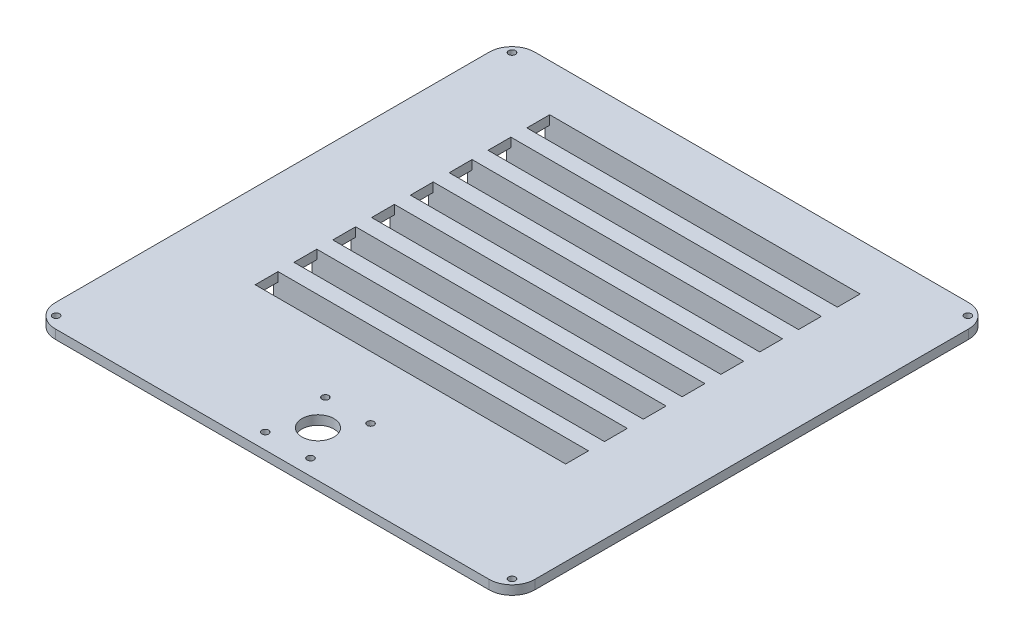
SolidWorks part; units mm, degrees
ref_plane "Front Plane" through (0, 0, 0) normal (0, 0, 1) x (1, 0, 0)
ref_plane "Top Plane" through (0, 0, 0) normal (0, 1, 0) x (1, 0, 0)
ref_plane "Right Plane" through (0, 0, 0) normal (1, 0, 0) x (0, 0, -1)
sketch "Sketch1" plane through (0, 0, 0) normal (0, 1, 0) x (1, 0, 0)
  line L0 (-101, -101) -> (-101, 101)
  line L5 (-105, -105) -> (105, -105)
  line L6 (-105, -105) -> (-105, 105)
  line L7 (-105, 105) -> (105, 105)
  line L8 (105, -105) -> (105, 105)
  line L9 (-101, 101) -> (101, 101)
  line L10 (101, -101) -> (101, 101)
  line L11 (-101, -101) -> (101, -101)
  line L12 (-101, 101) -> (-99.8333, 99.8333) construction
  line L13 (-55, 0) -> (55, 0) construction
  line L14 (-101, -101) -> (-99.8333, -99.8333) construction
  line L15 (0, -55) -> (0, 55) construction
  line L16 (101, -101) -> (99.8333, -99.8333) construction
  line L17 (101, 101) -> (99.8333, 99.8333) construction
  circle A1 centre (-99.8333, 99.8333) radius 1.5
  circle A2 centre (-99.8333, -99.8333) radius 1.5
  circle A3 centre (99.8333, -99.8333) radius 1.5
  circle A4 centre (99.8333, 99.8333) radius 1.5
  point P0 (0, 0)
  point P6 (-105, 0)
  point P7 (0, 105)
  dimension "D3" = 4
  dimension "D4" = 3
  dimension "D1" = 210
  dimension "D2" = 210
  dimension "D5" = 1.65
  dimension "D6" = 45
extrude "MainExtrude" add sketch "Sketch1" along normal blind 4 contours L6 L5 L8 L7
extrude "ScrewHoles" cut sketch "Sketch1<6>" along normal up to surface (4 mm away) contours A1 | A2 | A3 | A4 up to face at (0, 4, 0)
sketch "Sketch1<6>" plane through (0, 0, 0) normal (0, 1, 0) x (1, 0, 0) same geometry as "Sketch1"
fillet "RoundedCorners" radius 10 4 edges at (-105, 2, -105) (-105, 2, 105) (105, 2, -105) (105, 2, 105)
sketch "Sketch3" plane through (0, 0, 0) normal (0, 1, 0) x (1, 0, 0)
  line L145 (-68, 96.5) -> (68, 96.5) construction
  line L146 (-68, 96.5) -> (-68, -56.5) construction
  line L147 (-68, -56.5) -> (68, -56.5) construction
  line L148 (68, 96.5) -> (68, -56.5) construction
  line L149 (-68, 96.5) -> (68, -56.5) construction
  line L151 (68, 96.5) -> (-68, -56.5) construction
  line L152 (-68, 79.5) -> (68, 79.5) construction
  line L154 (-68, 62.5) -> (68, 62.5) construction
  line L155 (-68, 45.5) -> (68, 45.5) construction
  line L157 (-68, 28.5) -> (68, 28.5) construction
  line L158 (-68, 11.5) -> (68, 11.5) construction
  line L159 (-68, -5.5) -> (68, -5.5) construction
  line L160 (-68, -22.5) -> (68, -22.5) construction
  line L161 (-68, -39.5) -> (68, -39.5) construction
  line L162 (-68, 74.5) -> (68, 74.5)
  line L163 (-68, 57.5) -> (68, 57.5)
  line L164 (-68, 40.5) -> (68, 40.5)
  line L165 (-68, 23.5) -> (68, 23.5)
  line L166 (-68, 6.5) -> (68, 6.5)
  line L167 (-68, -10.5) -> (68, -10.5)
  line L168 (-68, -27.5) -> (68, -27.5)
  line L169 (-68, -44.5) -> (68, -44.5)
  line L170 (-68, 84.5) -> (68, 84.5)
  line L171 (-68, 67.5) -> (68, 67.5)
  line L172 (-68, 50.5) -> (68, 50.5)
  line L173 (-68, 33.5) -> (68, 33.5)
  line L174 (-68, 16.5) -> (68, 16.5)
  line L175 (-68, -0.5) -> (68, -0.5)
  line L176 (-68, -17.5) -> (68, -17.5)
  line L177 (-68, -34.5) -> (68, -34.5)
  line L178 (-68, 74.5) -> (-68, 84.5)
  line L179 (68, 74.5) -> (68, 84.5)
  line L180 (-68, 57.5) -> (-68, 67.5)
  line L181 (68, 57.5) -> (68, 67.5)
  line L182 (-68, 40.5) -> (-68, 50.5)
  line L183 (68, 40.5) -> (68, 50.5)
  line L184 (-68, 23.5) -> (-68, 33.5)
  line L185 (68, 23.5) -> (68, 33.5)
  line L186 (-68, 6.5) -> (-68, 16.5)
  line L187 (68, 6.5) -> (68, 16.5)
  line L188 (-68, -10.5) -> (-68, -0.5)
  line L189 (68, -10.5) -> (68, -0.5)
  line L190 (-68, -27.5) -> (-68, -17.5)
  line L191 (68, -27.5) -> (68, -17.5)
  line L192 (-68, -44.5) -> (-68, -34.5)
  line L193 (68, -44.5) -> (68, -34.5)
  line L194 (-99, -51) -> (-18, -51) construction
  line L195 (-99, -51) -> (-99, -94) construction
  line L196 (-99, -94) -> (-18, -94) construction
  line L197 (-18, -51) -> (-18, -94) construction
  line L198 (-99, -51) -> (-18, -94) construction
  line L199 (-99, -94) -> (-18, -51) construction
  line L200 (-9.9, -71.85) -> (-9.9, -98.15) construction
  line L201 (-95, -105) -> (95, -105) construction
  line L202 (-105, -95) -> (-105, 95) construction
  line L207 (-97.2358, 20) -> (95.5763, 20) construction
  line L208 (-9.9, -71.85) -> (9.9, -71.85) construction
  circle A0 centre (0, -85) radius 7
  circle A1 centre (-9.9, -71.85) radius 1.5
  circle A2 centre (-9.9, -98.15) radius 1.5
  circle A3 centre (9.9, -98.15) radius 1.5
  circle A4 centre (9.9, -71.85) radius 1.5
  circle A5 centre (-99.8333, -99.8333) radius 1.5 construction
  point P56 (-9.9, -85)
  point P69 (0, -71.85)
  point P70 (0, 20)
  point P71 (0, 0)
  dimension "D18" = 14
  dimension "D19" = 20
  dimension "D21" = 40.5
  dimension "D23" = 6
  dimension "D25" = 3
  dimension "D26" = 3
  dimension "D27" = 19.8
  dimension "D1" = 136
  dimension "D2" = 153
  dimension "D3" = 17
  dimension "D4" = 17
  dimension "D5" = 17
  dimension "D6" = 17
  dimension "D7" = 17
  dimension "D8" = 17
  dimension "D9" = 17
  dimension "D11" = 17
  dimension "D13" = 5
  dimension "D14" = 129
  dimension "D10" = 17
  dimension "D12" = 5
  dimension "D15" = 81
  dimension "D17" = 11
  dimension "D16" = 43
  dimension "D20" = 20
  dimension "D22" = 6.5
  dimension "D28" = 26.3
  dimension "D30" = 5.8333
extrude "Trench" cut sketch "Sketch3" along normal blind 10
sketch "Sketch4" plane through (0, 0, 0) normal (0, 1, 0) x (1, 0, 0)
  line L0 (68, -34.5) -> (68, -44.5) construction
  line L1 (68, -44.5) -> (-68, -44.5) construction
  line L2 (-68, -44.5) -> (-68, -34.5) construction
  line L3 (-68, -34.5) -> (68, -34.5) construction
  line L4 (68, -17.5) -> (68, -27.5) construction
  line L5 (68, -27.5) -> (-68, -27.5) construction
  line L6 (-68, -27.5) -> (-68, -17.5) construction
  line L7 (-68, -17.5) -> (68, -17.5) construction
  line L8 (68, -0.5) -> (68, -10.5) construction
  line L9 (68, -10.5) -> (-68, -10.5) construction
  line L10 (-68, -10.5) -> (-68, -0.5) construction
  line L11 (-68, -0.5) -> (68, -0.5) construction
  line L12 (68, 16.5) -> (68, 6.5) construction
  line L13 (68, 6.5) -> (-68, 6.5) construction
  line L14 (-68, 6.5) -> (-68, 16.5) construction
  line L15 (-68, 16.5) -> (68, 16.5) construction
  line L16 (68, 33.5) -> (68, 23.5) construction
  line L17 (68, 23.5) -> (-68, 23.5) construction
  line L18 (-68, 23.5) -> (-68, 33.5) construction
  line L19 (-68, 33.5) -> (68, 33.5) construction
  line L20 (68, 50.5) -> (68, 40.5) construction
  line L21 (68, 40.5) -> (-68, 40.5) construction
  line L22 (-68, 40.5) -> (-68, 50.5) construction
  line L23 (-68, 50.5) -> (68, 50.5) construction
  line L24 (68, 67.5) -> (68, 57.5) construction
  line L25 (68, 57.5) -> (-68, 57.5) construction
  line L26 (-68, 57.5) -> (-68, 67.5) construction
  line L27 (-68, 67.5) -> (68, 67.5) construction
  line L28 (68, 84.5) -> (68, 74.5) construction
  line L29 (68, 74.5) -> (-68, 74.5) construction
  line L30 (-68, 74.5) -> (-68, 84.5) construction
  line L31 (-68, 84.5) -> (68, 84.5) construction
  line L32 (68, -34.5) -> (68, -44.5)
  line L33 (68, -44.5) -> (-68, -44.5)
  line L34 (-68, -44.5) -> (-68, -34.5)
  line L35 (-68, -34.5) -> (68, -34.5)
  line L36 (68, -17.5) -> (68, -27.5)
  line L37 (68, -27.5) -> (-68, -27.5)
  line L38 (-68, -27.5) -> (-68, -17.5)
  line L39 (-68, -17.5) -> (68, -17.5)
  line L40 (68, -0.5) -> (68, -10.5)
  line L41 (68, -10.5) -> (-68, -10.5)
  line L42 (-68, -10.5) -> (-68, -0.5)
  line L43 (-68, -0.5) -> (68, -0.5)
  line L44 (68, 16.5) -> (68, 6.5)
  line L45 (68, 6.5) -> (-68, 6.5)
  line L46 (-68, 6.5) -> (-68, 16.5)
  line L47 (-68, 16.5) -> (68, 16.5)
  line L48 (68, 33.5) -> (68, 23.5)
  line L49 (68, 23.5) -> (-68, 23.5)
  line L50 (-68, 23.5) -> (-68, 33.5)
  line L51 (-68, 33.5) -> (68, 33.5)
  line L52 (68, 50.5) -> (68, 40.5)
  line L53 (68, 40.5) -> (-68, 40.5)
  line L54 (-68, 40.5) -> (-68, 50.5)
  line L55 (-68, 50.5) -> (68, 50.5)
  line L56 (68, 67.5) -> (68, 57.5)
  line L57 (68, 57.5) -> (-68, 57.5)
  line L58 (-68, 57.5) -> (-68, 67.5)
  line L59 (-68, 67.5) -> (68, 67.5)
  line L60 (68, 84.5) -> (68, 74.5)
  line L61 (68, 74.5) -> (-68, 74.5)
  line L62 (-68, 74.5) -> (-68, 84.5)
  line L63 (-68, 84.5) -> (68, 84.5)
  line L64 (70, 86.5) -> (70, 72.5)
  line L65 (70, 72.5) -> (-70, 72.5)
  line L66 (-70, 72.5) -> (-70, 86.5)
  line L67 (-70, 86.5) -> (70, 86.5)
  line L68 (70, 69.5) -> (70, 55.5)
  line L69 (70, 55.5) -> (-70, 55.5)
  line L70 (-70, 55.5) -> (-70, 69.5)
  line L71 (-70, 69.5) -> (70, 69.5)
  line L72 (70, 52.5) -> (70, 38.5)
  line L73 (70, 38.5) -> (-70, 38.5)
  line L74 (-70, 38.5) -> (-70, 52.5)
  line L75 (-70, 52.5) -> (70, 52.5)
  line L76 (70, 35.5) -> (70, 21.5)
  line L77 (70, 21.5) -> (-70, 21.5)
  line L78 (-70, 21.5) -> (-70, 35.5)
  line L79 (-70, 35.5) -> (70, 35.5)
  line L80 (70, 18.5) -> (70, 4.5)
  line L81 (70, 4.5) -> (-70, 4.5)
  line L82 (-70, 4.5) -> (-70, 18.5)
  line L83 (-70, 18.5) -> (70, 18.5)
  line L84 (70, 1.5) -> (70, -12.5)
  line L85 (70, -12.5) -> (-70, -12.5)
  line L86 (-70, -12.5) -> (-70, 1.5)
  line L87 (-70, 1.5) -> (70, 1.5)
  line L88 (70, -15.5) -> (70, -29.5)
  line L89 (70, -29.5) -> (-70, -29.5)
  line L90 (-70, -29.5) -> (-70, -15.5)
  line L91 (-70, -15.5) -> (70, -15.5)
  line L92 (70, -32.5) -> (70, -46.5)
  line L93 (70, -46.5) -> (-70, -46.5)
  line L94 (-70, -46.5) -> (-70, -32.5)
  line L95 (-70, -32.5) -> (70, -32.5)
  dimension "D1" = 2
extrude "Trench Walls" add sketch "Sketch4" against normal blind 4
sketch "Sketch5" plane through (0, -4, 0) normal (0, -1, 0) x (1, 0, 0)
  line L0 (-70, -86.5) -> (70, -86.5) construction
  line L1 (70, -86.5) -> (70, -72.5) construction
  line L2 (70, -72.5) -> (-70, -72.5) construction
  line L3 (-70, -72.5) -> (-70, -86.5) construction
  line L4 (-70, -69.5) -> (70, -69.5) construction
  line L5 (70, -69.5) -> (70, -55.5) construction
  line L6 (70, -55.5) -> (-70, -55.5) construction
  line L7 (-70, -55.5) -> (-70, -69.5) construction
  line L8 (-70, -52.5) -> (70, -52.5) construction
  line L9 (70, -52.5) -> (70, -38.5) construction
  line L10 (70, -38.5) -> (-70, -38.5) construction
  line L11 (-70, -38.5) -> (-70, -52.5) construction
  line L12 (-70, -35.5) -> (70, -35.5) construction
  line L13 (70, -35.5) -> (70, -21.5) construction
  line L14 (70, -21.5) -> (-70, -21.5) construction
  line L15 (-70, -21.5) -> (-70, -35.5) construction
  line L16 (-70, -18.5) -> (70, -18.5) construction
  line L17 (70, -18.5) -> (70, -4.5) construction
  line L18 (70, -4.5) -> (-70, -4.5) construction
  line L19 (-70, -4.5) -> (-70, -18.5) construction
  line L20 (-70, -1.5) -> (70, -1.5) construction
  line L21 (70, -1.5) -> (70, 12.5) construction
  line L22 (70, 12.5) -> (-70, 12.5) construction
  line L23 (-70, 12.5) -> (-70, -1.5) construction
  line L24 (-70, 15.5) -> (70, 15.5) construction
  line L25 (70, 15.5) -> (70, 29.5) construction
  line L26 (70, 29.5) -> (-70, 29.5) construction
  line L27 (-70, 29.5) -> (-70, 15.5) construction
  line L28 (-70, 32.5) -> (70, 32.5) construction
  line L29 (70, 32.5) -> (70, 46.5) construction
  line L30 (70, 46.5) -> (-70, 46.5) construction
  line L31 (-70, 46.5) -> (-70, 32.5) construction
  line L32 (-70, -86.5) -> (70, -86.5)
  line L33 (70, -86.5) -> (70, -72.5)
  line L34 (70, -72.5) -> (-70, -72.5)
  line L35 (-70, -72.5) -> (-70, -86.5)
  line L36 (-70, -69.5) -> (70, -69.5)
  line L37 (70, -69.5) -> (70, -55.5)
  line L38 (70, -55.5) -> (-70, -55.5)
  line L39 (-70, -55.5) -> (-70, -69.5)
  line L40 (-70, -52.5) -> (70, -52.5)
  line L41 (70, -52.5) -> (70, -38.5)
  line L42 (70, -38.5) -> (-70, -38.5)
  line L43 (-70, -38.5) -> (-70, -52.5)
  line L44 (-70, -35.5) -> (70, -35.5)
  line L45 (70, -35.5) -> (70, -21.5)
  line L46 (70, -21.5) -> (-70, -21.5)
  line L47 (-70, -21.5) -> (-70, -35.5)
  line L48 (-70, -18.5) -> (70, -18.5)
  line L49 (70, -18.5) -> (70, -4.5)
  line L50 (70, -4.5) -> (-70, -4.5)
  line L51 (-70, -4.5) -> (-70, -18.5)
  line L52 (-70, -1.5) -> (70, -1.5)
  line L53 (70, -1.5) -> (70, 12.5)
  line L54 (70, 12.5) -> (-70, 12.5)
  line L55 (-70, 12.5) -> (-70, -1.5)
  line L56 (-70, 15.5) -> (70, 15.5)
  line L57 (70, 15.5) -> (70, 29.5)
  line L58 (70, 29.5) -> (-70, 29.5)
  line L59 (-70, 29.5) -> (-70, 15.5)
  line L60 (-70, 32.5) -> (70, 32.5)
  line L61 (70, 32.5) -> (70, 46.5)
  line L62 (70, 46.5) -> (-70, 46.5)
  line L63 (-70, 46.5) -> (-70, 32.5)
extrude "Trench Bottom" add sketch "Sketch5" along normal blind 2
sketch "Sketch7" plane through (70, 0, 0) normal (1, 0, 0) x (0, 0, -1)
  line L1 (-44.5, 0) -> (-34.5, 0)
  line L2 (-44.5, 0) -> (-44.5, -6)
  line L3 (-44.5, -6) -> (-34.5, -6)
  line L4 (-34.5, 0) -> (-34.5, -6)
  line L5 (-46.5, -6) -> (-46.5, 0) construction
  line L6 (-32.5, -6) -> (-46.5, -6) construction
  line L7 (-27.5, 0) -> (-27.5, -6)
  line L8 (-27.5, 0) -> (-17.5, 0)
  line L9 (-17.5, 0) -> (-17.5, -6)
  line L10 (-27.5, -6) -> (-17.5, -6)
  line L11 (-10.5, 0) -> (-10.5, -6)
  line L12 (-10.5, 0) -> (-0.5, 0)
  line L13 (-0.5, 0) -> (-0.5, -6)
  line L14 (-10.5, -6) -> (-0.5, -6)
  line L15 (6.5, 0) -> (6.5, -6)
  line L16 (6.5, 0) -> (16.5, 0)
  line L17 (16.5, 0) -> (16.5, -6)
  line L18 (6.5, -6) -> (16.5, -6)
  line L19 (23.5, 0) -> (23.5, -6)
  line L20 (23.5, 0) -> (33.5, 0)
  line L21 (33.5, 0) -> (33.5, -6)
  line L22 (23.5, -6) -> (33.5, -6)
  line L23 (40.5, 0) -> (40.5, -6)
  line L24 (40.5, 0) -> (50.5, 0)
  line L25 (50.5, 0) -> (50.5, -6)
  line L26 (40.5, -6) -> (50.5, -6)
  line L27 (57.5, 0) -> (57.5, -6)
  line L28 (57.5, 0) -> (67.5, 0)
  line L29 (67.5, 0) -> (67.5, -6)
  line L30 (57.5, -6) -> (67.5, -6)
  line L31 (74.5, 0) -> (74.5, -6)
  line L32 (74.5, 0) -> (84.5, 0)
  line L33 (84.5, 0) -> (84.5, -6)
  line L34 (74.5, -6) -> (84.5, -6)
  line L35 (-29.5, -6) -> (-29.5, 0) construction
  line L36 (-46.5, 0) -> (-32.5, 0) construction
  dimension "D3" = 10
  dimension "D4" = 2
  dimension "D5" = 8
  dimension "D6" = 2
extrude "Wire Opening" cut sketch "Sketch7" against normal through all both and the other way through all
equation "\"1_LED\"= 17mm"
equation "\"2_LED\"= \"1_LED\" * 2"
equation "\"3_LED\"= \"1_LED\" * 3"
equation "\"4_LED\"= \"1_LED\" * 4"
equation "\"5_LED\"= \"1_LED\" * 5"
equation "\"6_LED\"= \"1_LED\" * 6"
equation "\"7_LED\"= \"1_LED\" * 7"
equation "\"8_LED\"= \"1_LED\" * 8"
equation "\"9_LED\"= \"1_LED\" * 9"
equation "\"10_LED\"= \"1_LED\" * 10"
equation "\"11_LED\"= \"1_LED\" * 11"
equation "\"12_LED\"= \"1_LED\" * 12"
